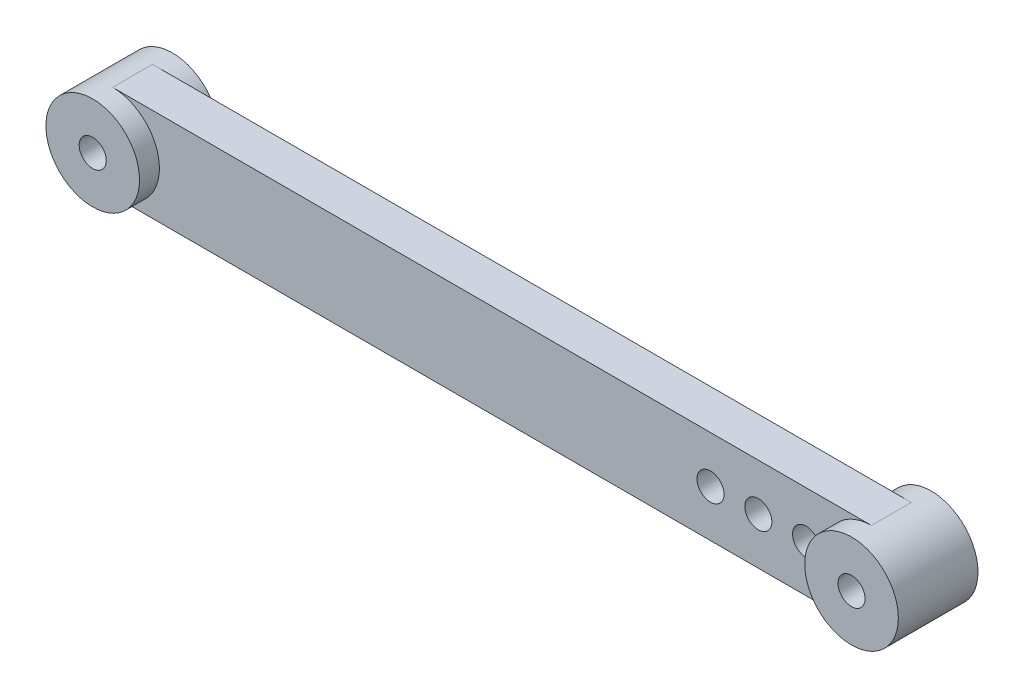
SolidWorks part; units mm, degrees
ref_plane "Front Plane" through (0, 0, 0) normal (0, 0, 1) x (1, 0, 0)
ref_plane "Top Plane" through (0, 0, 0) normal (0, 1, 0) x (1, 0, 0)
ref_plane "Right Plane" through (0, 0, 0) normal (1, 0, 0) x (0, 0, -1)
sketch "Sketch1" plane through (0, 0, 0) normal (0, 0, 1) x (1, 0, 0)
  line L0 (-47.625, 0) -> (47.625, 0) construction
  line L1 (-47.625, 5.875) -> (47.625, 5.875)
  line L2 (-47.625, -5.875) -> (47.625, -5.875)
  arc A0 (-47.625, 5.875) -> (-47.625, -5.875) centre (-47.625, 0) ccw
  arc A1 (47.625, -5.875) -> (47.625, 5.875) centre (47.625, 0) ccw
  point P2 (0, 0)
  dimension "D1" = 11.75
  dimension "D2" = 95.25
extrude "Boss-Extrude1" add sketch "Sketch1" along normal mid plane 5
sketch "Sketch3" plane through (0, 0, 0) normal (0, 0, 1) x (1, 0, 0)
  circle A0 centre (-47.625, 0) radius 5.875
  circle A1 centre (47.625, 0) radius 5.875
extrude "Boss-Extrude2" add sketch "Sketch3" along normal mid plane 10
sketch "Sketch2" plane through (0, 0, 0) normal (0, 0, 1) x (1, 0, 0)
  circle A0 centre (-47.625, 0) radius 1.7
  circle A1 centre (47.625, 0) radius 1.7
  arc A3 (-47.625, -5.875) -> (-47.625, 5.875) centre (-47.625, 0) ccw construction
  arc A4 (47.625, 5.875) -> (47.625, -5.875) centre (47.625, 0) ccw construction
  dimension "D1" = 3.4
  dimension "D2" = 3.4
extrude "Cut-Extrude1" cut sketch "Sketch2" against normal through all both and the other way through all
sketch "Sketch4" plane through (0, 0, 2.5) normal (0, 0, 1) x (1, 0, 0)
  line L0 (49.325, 0) -> (0, 0) construction
  circle A0 centre (33.425, 0) radius 1.7
  circle A1 centre (47.625, 0) radius 1.7 construction
  circle A2 centre (27.425, 0) radius 1.7
  circle A3 centre (39.425, 0) radius 1.7
  point P8 (0, 0)
  point P13 (0, 0)
  point P14 (0, 0)
  point P15 (0, 0)
  point P16 (0, 0)
  dimension "D1" = 3.4
  dimension "D3" = 3.4
  dimension "D4" = 3.4
  dimension "D2" = 14.2
  dimension "D5" = 6
  dimension "D6" = 6
extrude "Cut-Extrude2" cut sketch "Sketch4" against normal through all both and the other way through all
